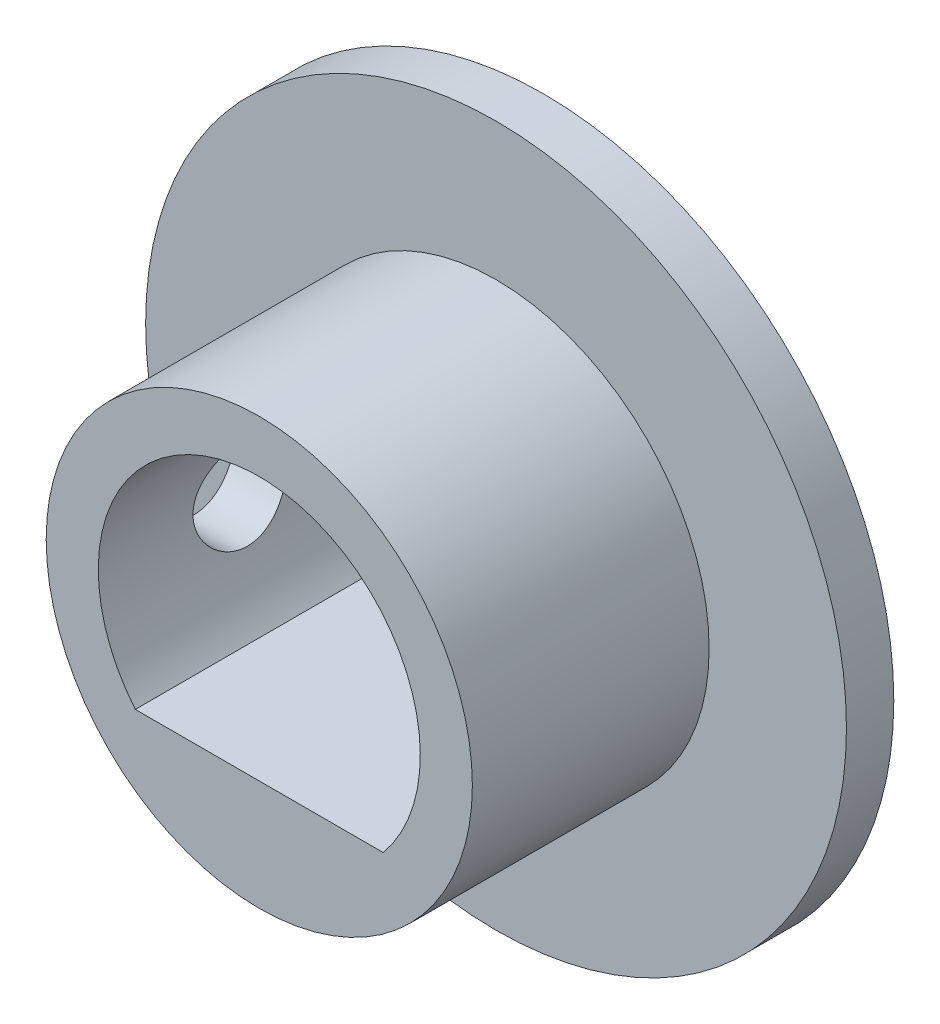
SolidWorks part; units mm, degrees
ref_plane "Plano frontal" through (0, 0, 0) normal (0, 0, 1) x (1, 0, 0)
ref_plane "Plano superior" through (0, 0, 0) normal (0, 1, 0) x (1, 0, 0)
ref_plane "Plano direito" through (0, 0, 0) normal (1, 0, 0) x (0, 0, -1)
sketch "Esboço1" plane through (0, 0, 0) normal (0, 0, 1) x (1, 0, 0)
  line L0 (-1.2114, -0.8846) -> (1.2114, -0.8846)
  arc A0 (1.2114, -0.8846) -> (-1.2114, -0.8846) centre (0, 0) ccw
  circle A1 centre (0, 0) radius 3.7
  dimension "D1" = 3
  dimension "D3" = 7.4
extrude "Ressalto-extrusão2" add sketch "Esboço1" along normal blind 6.5 contours A1 A0 region at (-3.5953, 0, 0)
sketch "Esboço2" plane through (0, 0, 0) normal (0, 0, -1) x (-1, 0, 0)
  circle A0 centre (0, 0) radius 1.875
  dimension "D1" = 3.75
extrude "Corte-extrusão1" cut sketch "Esboço2" against normal blind 0.6
sketch "Esboço3" plane through (0, 0, 6.5) normal (0, 0, 1) x (1, 0, 0)
  circle A0 centre (0, 0) radius 2.415
  circle A3 centre (0, 0) radius 5
  dimension "D1" = 10
extrude "Corte-extrusão2" cut sketch "Esboço3" against normal blind 5.5
sketch "Esboço6" plane through (0, 0, 0) normal (0, 0, -1) x (-1, 0, 0)
  circle A0 centre (0, 0) radius 2.05
  dimension "D1" = 4.1
extrude "Corte-extrusão6" cut sketch "Esboço6" against normal blind 0.9
sketch "Esboço7" plane through (0, 0, 6.5) normal (0, 0, 1) x (1, 0, 0)
  circle A0 centre (0, 0) radius 2.1
  circle A1 centre (0, 0) radius 2.415
  dimension "D1" = 4.2
extrude "Corte-extrusão7" cut sketch "Esboço7" against normal up to surface (5.5 mm away) up to face at (2.415, 0, 1)
sketch "Esboço8" plane through (0, 0, 1) normal (0, 0, 1) x (1, 0, 0)
  circle A0 centre (0, 0) radius 2.25
  circle A1 centre (0, 0) radius 2.1
  dimension "D1" = 4.5
extrude "Ressalto-extrusão3" add sketch "Esboço8" along normal blind 3.5
sketch "Esboço11" plane through (0, 0, 1) normal (0, 0, 1) x (1, 0, 0)
  circle A0 centre (0, 0) radius 2.65
  circle A2 centre (0, 0) radius 2.25 construction
  circle A3 centre (0, 0) radius 2.25
  dimension "D1" = 5.3
extrude "Ressalto-extrusão4" add sketch "Esboço11" along normal blind 3.5
sketch "Esboço9" plane through (0, 0, 0) normal (1, 0, 0) x (0, 0, -1)
  circle A2 centre (-2, 0) radius 0.5
  dimension "D1" = 1
extrude "Corte-extrusão8" cut sketch "Esboço9" against normal blind 10
sketch "Esboço13" plane through (0, 0, 0) normal (0, 0, -1) x (-1, 0, 0)
  circle A1 centre (0, 0) radius 3.7
  circle A2 centre (0, 0) radius 3.7
  dimension "D1" = 0
extrude "Corte-extrusão10" cut sketch "Esboço13" against normal blind 0.5
sketch "Esboço14" plane through (0, 0, 0.9) normal (0, 0, -1) x (-1, 0, 0)
  circle A1 centre (0, 0) radius 2.05
  circle A3 centre (0, 0) radius 2.05
  dimension "D1" = 0
extrude "Corte-extrusão11" cut sketch "Esboço14" against normal blind 0.4
sketch "Esboço15" plane through (0, 0, 0) normal (0, 1, 0) x (1, 0, 0)
  line L0 (-2.65, -4.5) -> (2.65, -4.5) construction
  line L1 (2.65, -4.5) -> (-2.65, -4.5)
  line L2 (2.65, -4.5) -> (2.65, -6.778)
  line L3 (2.65, -6.778) -> (-2.65, -6.778)
  line L4 (-2.65, -4.5) -> (-2.65, -6.778)
extrude "Corte-extrusão12" cut sketch "Esboço15" against normal mid plane 10.4
sketch "Esboço17" plane through (0, 0, 1.3) normal (0, 0, -1) x (-1, 0, 0)
  line L0 (-1.2114, -0.8846) -> (1.2114, -0.8846) construction
  line L1 (-1.2114, -0.8846) -> (1.2114, -0.8846)
  arc A0 (1.2114, -0.8846) -> (-1.2114, -0.8846) centre (0, 0) ccw construction
  circle A1 centre (0, 0) radius 2.05
  circle A2 centre (0, 0) radius 2.05
  arc A3 (1.2114, -0.8846) -> (-1.2114, -0.8846) centre (0, 0) ccw
  dimension "D1" = 0
extrude "Ressalto-extrusão6" add sketch "Esboço17" along normal up to surface (0.8 mm away) up to face at (-3.7, 0, 0.5)
sketch "Esboço18" plane through (0, 0, 4.5) normal (0, 0, 1) x (1, 0, 0)
  circle A3 centre (0, 0) radius 2.25
  circle A5 centre (0, 0) radius 2.65
  dimension "D1" = 4.5
extrude "Corte-extrusão13" cut sketch "Esboço18" against normal up to surface (3.5 mm away) up to face at (3.7, 0, 1)
sketch "Esboço19" plane through (0, 0, 0) normal (1, 0, 0) x (0, 0, -1)
  line L1 (-3.5, -3.3006) -> (-4.7601, -3.3006)
  line L2 (-3.5, -3.3006) -> (-3.5, 3.0534)
  line L3 (-3.5, 3.0534) -> (-4.7601, 3.0534)
  line L4 (-4.7601, -3.3006) -> (-4.7601, 3.0534)
  dimension "D1" = 1
extrude "Corte-extrusão14" cut sketch "Esboço19" against normal mid plane 10
sketch "Esboço20" plane through (0, 0, 0.5) normal (0, 0, -1) x (-1, 0, 0)
  line L2 (-1.309, -1.0846) -> (1.309, -1.0846)
  line L3 (-1.309, -1.0846) -> (1.309, -1.0846)
  arc A3 (1.309, -1.0846) -> (-1.309, -1.0846) centre (0, 0) ccw
  arc A4 (1.309, -1.0846) -> (-1.309, -1.0846) centre (0, 0) ccw
  dimension "D1" = 0.2
extrude "Corte-extrusão15" cut sketch "Esboço20" against normal blind 10
